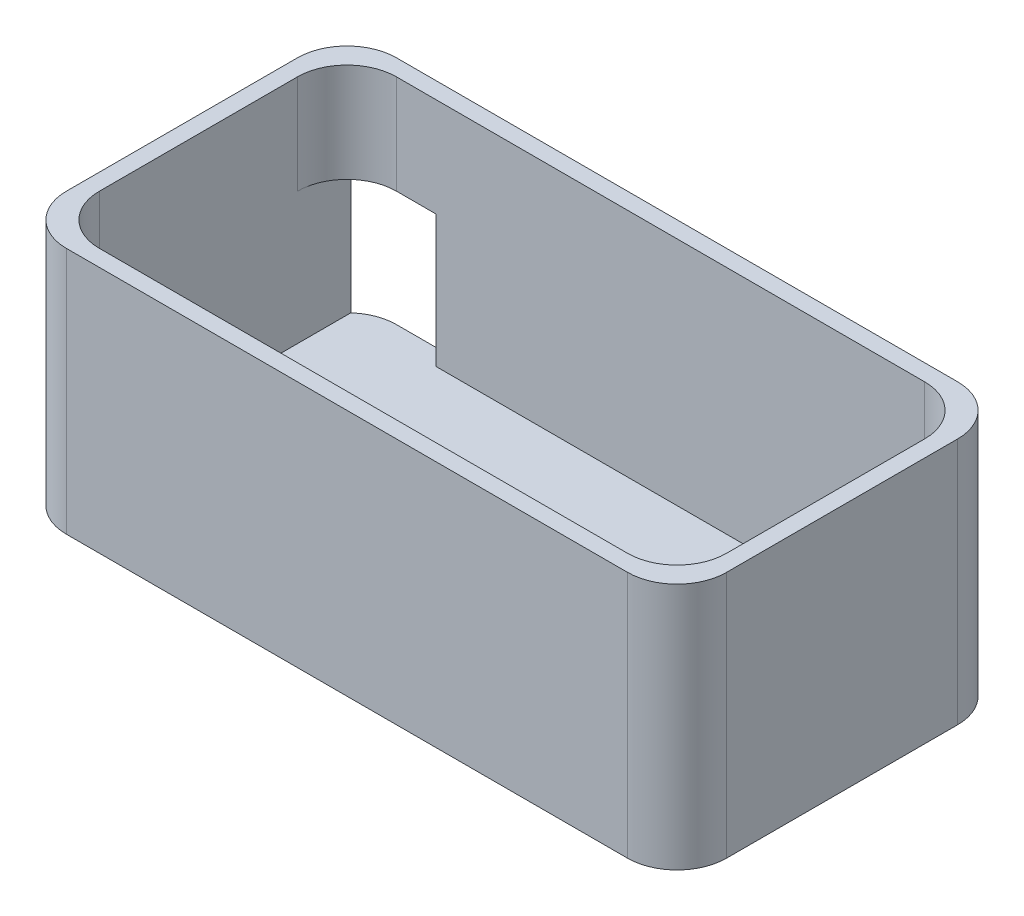
SolidWorks part; units mm, degrees
ref_plane "Front Plane" through (0, 0, 0) normal (0, 0, 1) x (1, 0, 0)
ref_plane "Top Plane" through (0, 0, 0) normal (0, 1, 0) x (1, 0, 0)
ref_plane "Right Plane" through (0, 0, 0) normal (1, 0, 0) x (0, 0, -1)
sketch "Sketch1" plane through (0, 0, 0) normal (0, 1, 0) x (1, 0, 0)
  line L1 (-100, 50) -> (100, 50)
  line L2 (-100, 50) -> (-100, -50)
  line L3 (-100, -50) -> (100, -50)
  line L4 (100, 50) -> (100, -50)
  line L5 (-100, 50) -> (100, -50) construction
  line L6 (-100, -50) -> (100, 50) construction
  point P0 (0, 0)
  dimension "D1" = 200
  dimension "D2" = 100
extrude "Boss-Extrude1" add sketch "Sketch1" along normal blind 5
sketch "Sketch2" plane through (0, 5, 0) normal (0, 1, 0) x (1, 0, 0)
  line L1 (-100, 50) -> (100, 50)
  line L2 (-100, 50) -> (-100, -50)
  line L3 (-100, -50) -> (100, -50)
  line L4 (100, 50) -> (100, -50)
  line L5 (-100, 50) -> (100, -50) construction
  line L6 (-100, -50) -> (100, 50) construction
  line L7 (-95, 45) -> (95, 45)
  line L8 (-95, 45) -> (-95, -45)
  line L9 (-95, -45) -> (95, -45)
  line L10 (95, 45) -> (95, -45)
  line L11 (-95, 45) -> (95, -45) construction
  line L12 (-95, -45) -> (95, 45) construction
  point P0 (0, 0)
  point P5 (0, 0)
  dimension "D1" = 5
  dimension "D2" = 5
extrude "Boss-Extrude2" add sketch "Sketch2" along normal blind 70
sketch "Sketch3" plane through (0, 0, -45) normal (0, 0, 1) x (1, 0, 0)
  line L1 (-95, 5) -> (-68, 5)
  line L2 (-95, 5) -> (-95, 45)
  line L3 (-95, 45) -> (-68, 45)
  line L4 (-68, 5) -> (-68, 45)
  point P4 (-95, 5)
  dimension "D1" = 40
  dimension "D2" = 27
extrude "Cut-Extrude1" cut sketch "Sketch3" against normal through all
fillet "Fillet1" radius 15 8 edges at (95, 40, 45) (95, 40, -45) (100, 37.5, -50) (-100, 37.5, -50) (-95, 60, -45) (-95, 40, 45) (100, 37.5, 50) (-100, 37.5, 50)
